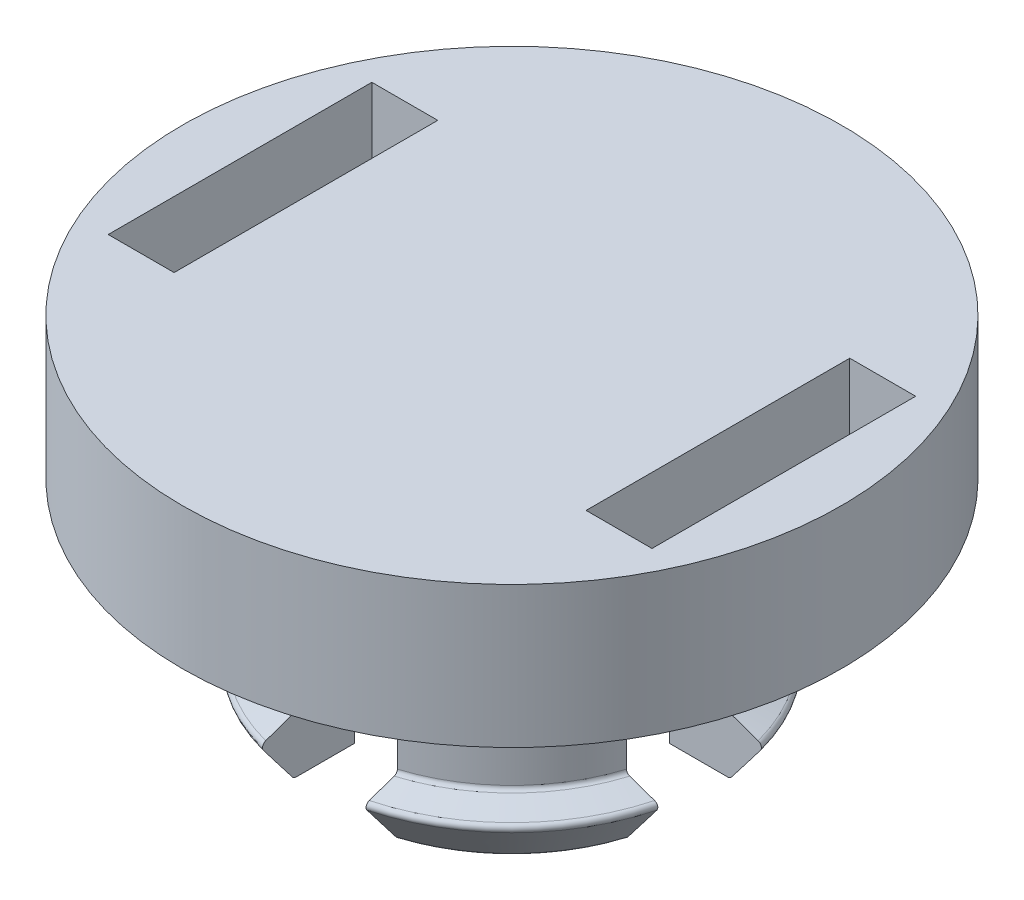
SolidWorks part; units mm, degrees
ref_plane "Front Plane" through (0, 0, 0) normal (0, 0, 1) x (1, 0, 0)
ref_plane "Top Plane" through (0, 0, 0) normal (0, 1, 0) x (1, 0, 0)
ref_plane "Right Plane" through (0, 0, 0) normal (1, 0, 0) x (0, 0, -1)
sketch "Szkic1" plane through (0, 0, 0) normal (0, 1, 0) x (1, 0, 0)
  circle A0 centre (0, 0) radius 7
  dimension "D1" = 14
extrude "Dodanie-wyciągnięcie1" add sketch "Szkic1" along normal blind 3
ref_point "Punkt1"
ref_plane "Płaszczyzna1" through (0, 0, 0) normal (0, -1, 0) x (-1, 0, 0)
sketch "Szkic2" plane through (0, 0, 0) normal (0, -1, 0) x (-1, 0, 0)
  circle A0 centre (0, 0) radius 3.7
  dimension "D1" = 7.4
extrude "Dodanie-wyciągnięcie2" add sketch "Szkic2" along normal blind 4.3
ref_axis "Oś1" through (0, -4.3, 0) along (0, 1, 0)
sketch "Szkic3" plane through (0, 0, 0) normal (1, 0, 0) x (0, 0, -1)
  line L1 (3.7, -4.3) -> (4.4, -3.3548)
  line L2 (4.4, -3.3548) -> (3.7, -3.1)
  line L4 (3.7, -3.1) -> (3.7, -4.3)
  line L5 (0, -4.3) -> (0, 0) construction
  line L7 (-7.7, 0) -> (7.7, 0) construction
  dimension "D1" = 3.7
  dimension "D2" = 1.2
  dimension "D3" = 70
  dimension "D4" = 4.3
  dimension "D5" = 4.4
revolve "Obrót1" add sketch "Szkic3" angle 360 about axis through (0, -4.3, 0) along (0, 1, 0)
fillet "Zaokrąglenie1" radius 0.1 3 edges at (0, -3.3548, -4.4) (0, -3.1, -3.7) (0, -4.3, -3.7)
ref_plane "Płaszczyzna2" through (0, -4.3, 0) normal (0, -1, 0) x (-1, 0, 0)
sketch "Szkic5" plane through (0, -4.3, 0) normal (0, -1, 0) x (-1, 0, 0)
  line L0 (-7.9807, -1.1) -> (-1.1, -1.1)
  line L1 (7.9807, 1.1) -> (1.1, 1.1)
  line L2 (-1.1, -7.9807) -> (-1.1, -1.1)
  line L3 (1.1, 7.9807) -> (1.1, 1.1)
  line L4 (-1.1, 1.1) -> (-1.1, 7.9807)
  line L5 (1.1, -1.1) -> (7.9807, -1.1)
  line L6 (1.1, -1.1) -> (1.1, -7.9807)
  line L7 (-1.1, 1.1) -> (-7.9807, 1.1)
  line L8 (-1.1, -1.1) -> (1.1, 1.1) construction
  arc A0 (-7.9807, 1.1) -> (-7.9807, -1.1) centre (0, 0) ccw
  arc A1 (-1.1, -7.9807) -> (1.1, -7.9807) centre (0, 0) ccw
  arc A2 (7.9807, -1.1) -> (7.9807, 1.1) centre (0, 0) ccw
  arc A3 (1.1, 7.9807) -> (-1.1, 7.9807) centre (0, 0) ccw
  circle A4 centre (0, 0) radius 2.5
  point P1 (0, 0)
  dimension "D3" = 5
  dimension "D1" = 2.2
  dimension "D2" = 2.2
extrude "Wytnij-wyciągnięcie1" cut sketch "Szkic5" against normal up to surface (4.3 mm away) contours L4 A4 L7 | L8 L2 A4 L6 L5 L1 | L0 L8 L3 A4 L4 L7 | L1 A4 L3 | A4 L5 A2 L1 | A4 L3 A3 L4 | A4 L7 A0 L0 | A4 L2 A1 L6 | L6 A4 L5 | L0 A4 L2 region at (5.2235, -4.3, 0) region at (0.729, -4.3, -0.729) region at (1.5234, -4.3, 1.5234) region at (-0.729, -4.3, 0.729) region at (1.5234, -4.3, -1.5234) region at (0, -4.3, 5.2235) region at (-1.5234, -4.3, -1.5234) region at (0, -4.3, -5.2235) region at (-1.5234, -4.3, 1.5234) region at (-5.2235, -4.3, 0) up to face at (0, 0, -3.7)
ref_plane "płaszczyzna dolna" through (0, 3, 0) normal (0, 1, 0) x (1, 0, 0)
sketch "Szkic8" plane through (0, 3, 0) normal (0, 1, 0) x (1, 0, 0)
  line L0 (4.375, -2.8) -> (-4.375, 2.8) construction
  line L1 (5.775, -2.8) -> (4.375, -2.8)
  line L2 (5.775, -2.8) -> (5.775, 2.8)
  line L3 (5.775, 2.8) -> (4.375, 2.8)
  line L4 (4.375, -2.8) -> (4.375, 2.8)
  line L5 (-4.375, -2.8) -> (-5.775, -2.8)
  line L6 (-4.375, -2.8) -> (-4.375, 2.8)
  line L7 (-4.375, 2.8) -> (-5.775, 2.8)
  line L8 (-5.775, -2.8) -> (-5.775, 2.8)
  point P8 (0, 0)
  dimension "D1" = 5.6
  dimension "D2" = 1.4
  dimension "D3" = 8.75
extrude "Wytnij-wyciągnięcie2" cut sketch "Szkic8" against normal blind 2.3
sketch "Szkic10" plane through (5.775, 0, 0) normal (-1, 0, 0) x (0, 0, 1)
  line L0 (-2.8, 1.2) -> (-2.8, 0.7)
  line L1 (-2.8, 0.7) -> (-2.8, 3) construction
  line L2 (-2.8, 0.7) -> (0, 0.7)
  line L3 (2.8, 0.7) -> (-2.8, 0.7) construction
  line L4 (0, 0.7) -> (2.8, 0.7)
  line L5 (2.8, 0.7) -> (2.8, 1.2)
  line L7 (2.8, 1.2) -> (0, 0.7)
  line L8 (-2.8, 1.2) -> (0, 0.7)
  line L9 (2.8, 0.7) -> (2.8, 3) construction
  line M6 (-2.8, 3) -> (-2.8, 0.7)
  line M7 (-2.8, 0.7) -> (2.8, 0.7)
  line M8 (2.8, 0.7) -> (2.8, 3)
  dimension "D1" = 0.5
extrude "Dodanie-wyciągnięcie3" add sketch "Szkic10" along normal blind 12 contours L8 M6 M7 | L7 M8 M7 region at (5.775, 0.8667, -1.8667) region at (5.775, 0.8667, 1.8667)
equation "\".18.90mm\"=18.9"
